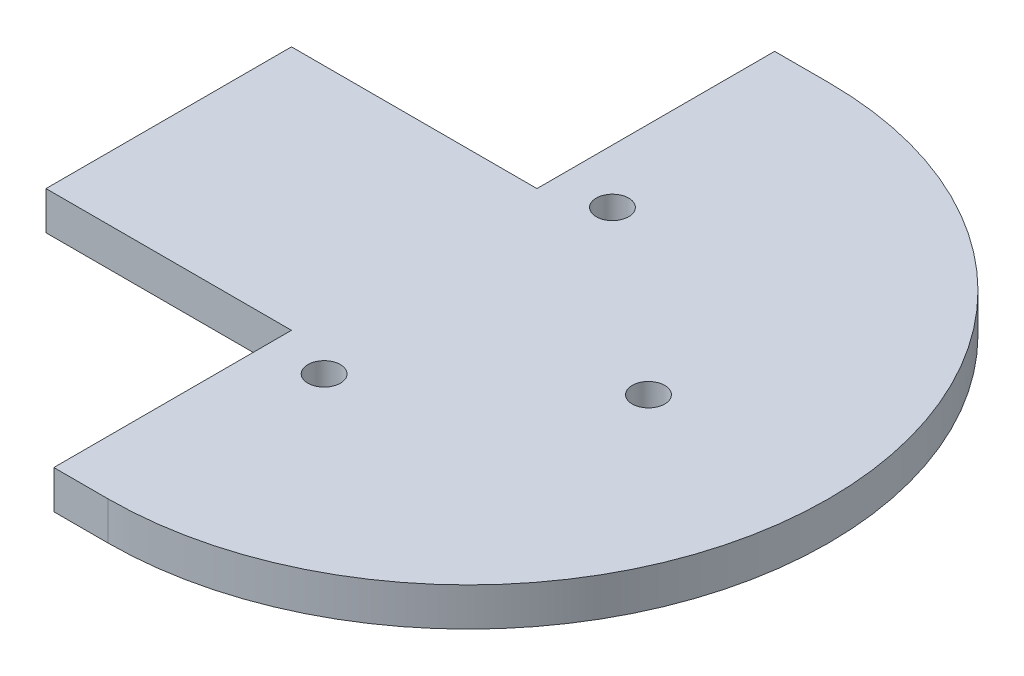
SolidWorks part; units mm, degrees
ref_plane "Front Plane" through (0, 0, 0) normal (0, 0, 1) x (1, 0, 0)
ref_plane "Top Plane" through (0, 0, 0) normal (0, 1, 0) x (1, 0, 0)
ref_plane "Right Plane" through (0, 0, 0) normal (1, 0, 0) x (0, 0, -1)
sketch "Sketch1" plane through (0, 0, 0) normal (0, 1, 0) x (1, 0, 0)
  line L0 (-14.1213, -33.9089) -> (-14.1213, -50.6589)
  line L1 (-31.4213, -16.6089) -> (-14.1213, -16.6089)
  line L2 (-31.4213, -16.6089) -> (-31.4213, -33.9089)
  line L3 (-31.4213, -33.9089) -> (-14.1213, -33.9089)
  line L4 (-31.4213, -25.2589) -> (15.0887, -25.2589) construction
  line L6 (-10.3113, -15.0989) -> (-10.3113, -35.4189) construction
  line L8 (-10.3113, 0.1411) -> (-14.1213, 0.1411)
  line L10 (-10.3113, -50.6589) -> (-14.1213, -50.6589)
  line L11 (-14.1213, 0.1411) -> (-14.1213, -16.6089)
  arc A0 (-10.3113, -50.6589) -> (-10.3113, 0.1411) centre (-10.3113, -25.2589) ccw
  circle A1 centre (-10.3113, -15.0989) radius 1.143
  circle A2 centre (-10.3113, -35.4189) radius 1.143
  circle A3 centre (2.3887, -25.2589) radius 1.143
  point P15 (-10.3113, -25.2589)
  point P18 (0, 0)
  dimension "D3" = 50.8
  dimension "D1" = 2.286
  dimension "D2" = 20.32
  dimension "D4" = 12.7
  dimension "D5" = 3.81
  dimension "D6" = 17.3
  dimension "D7" = 3.81
extrude "Boss-Extrude1" add sketch "Sketch1" along normal blind 2.7
